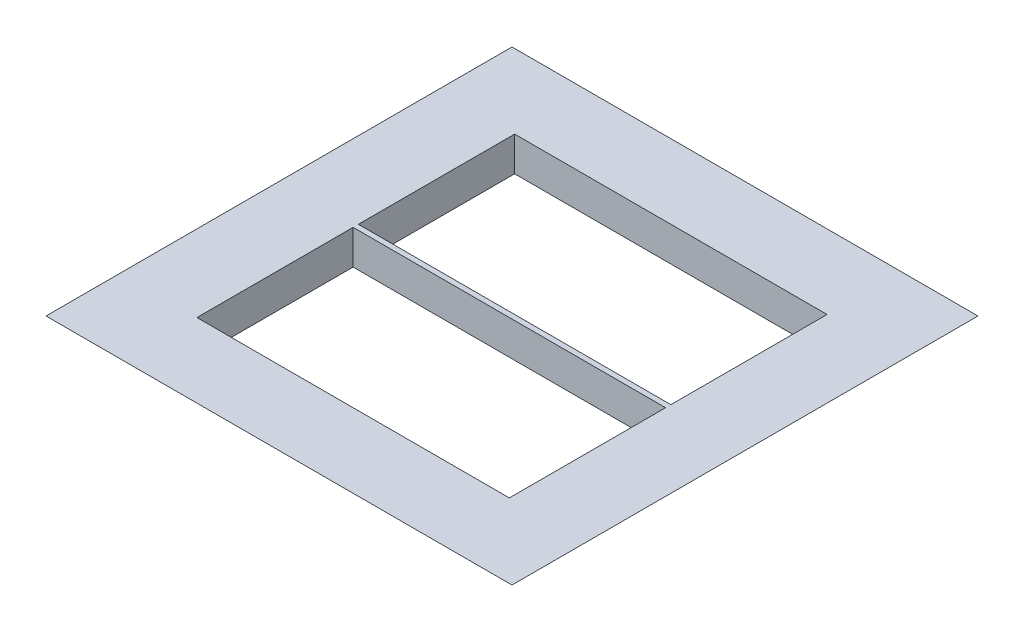
SolidWorks part; units mm, degrees
ref_plane "Front Plane" through (0, 0, 0) normal (0, 0, 1) x (1, 0, 0)
ref_plane "Top Plane" through (0, 0, 0) normal (0, 1, 0) x (1, 0, 0)
ref_plane "Right Plane" through (0, 0, 0) normal (1, 0, 0) x (0, 0, -1)
sketch "Sketch1" plane through (0, 0, 0) normal (0, 1, 0) x (1, 0, 0)
  line L1 (0, 0) -> (150, 0)
  line L2 (0, 0) -> (0, 150)
  line L3 (0, 150) -> (150, 150)
  line L4 (150, 0) -> (150, 150)
extrude "Boss-Extrude1" add sketch "Sketch1" along normal blind 13 draft 45 draft outward yes
sketch "Sketch2" plane through (0, 13, 0) normal (0, 1, 0) x (1, 0, 0)
  line L0 (-13, 75) -> (163, 75) construction
  line L1 (-13, 163) -> (-13, -13) construction
  line L2 (163, -13) -> (163, 163) construction
  line L3 (16.1123, 23.7215) -> (-13, 23.7215) construction
  line L4 (-13, -13) -> (163, -13) construction
  line L5 (75, 163) -> (75, -13) construction
  line L6 (163, 163) -> (-13, 163) construction
  line L7 (16, 74) -> (134, 74)
  line L8 (16, 74) -> (16, 15)
  line L9 (16, 15) -> (134, 15)
  line L10 (134, 74) -> (134, 15)
  line L11 (133.8877, 22.2798) -> (163, 22.2798) construction
  line L12 (134, 76) -> (134, 135)
  line L13 (27.0447, 15) -> (27.0447, -13) construction
  line L14 (16, 135) -> (134, 135)
  line L15 (16, 76) -> (16, 135)
  line L16 (16, 76) -> (134, 76)
extrude "Cut-Extrude1" cut sketch "Sketch2" against normal blind 13
